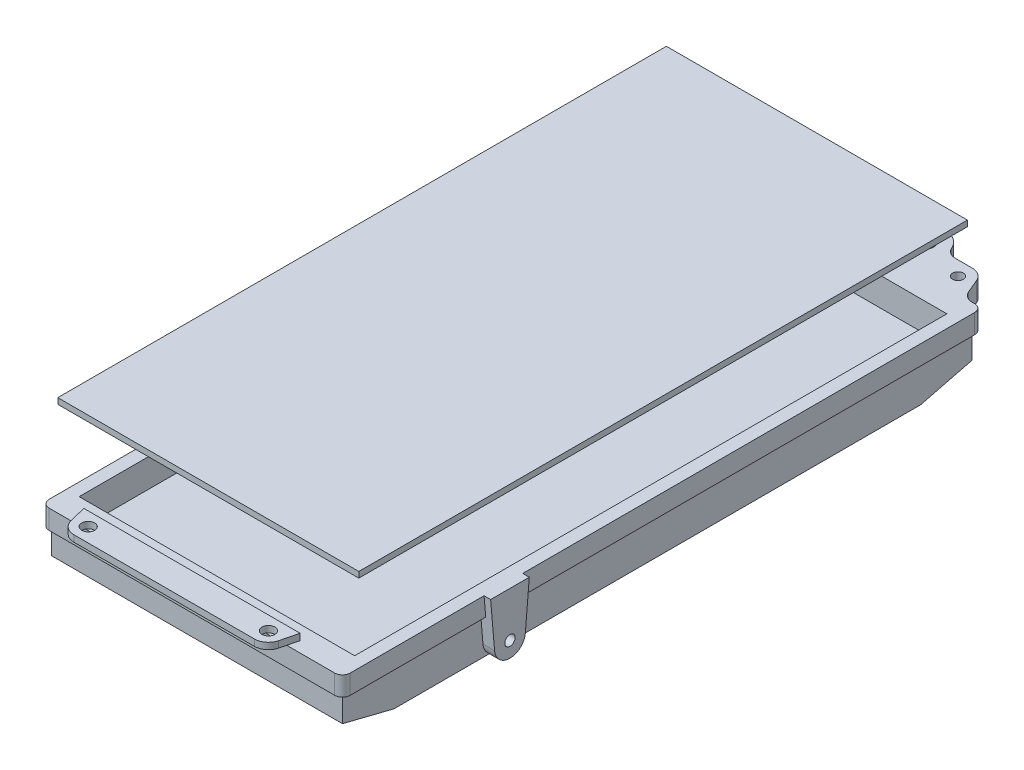
SolidWorks part; units mm, degrees
ref_plane "前视基准面" through (0, 0, 0) normal (0, 0, 1) x (1, 0, 0)
ref_plane "上视基准面" through (0, 0, 0) normal (0, 1, 0) x (1, 0, 0)
ref_plane "右视基准面" through (0, 0, 0) normal (1, 0, 0) x (0, 0, -1)
sketch "草图1" plane through (0, 0, 0) normal (0, 1, 0) x (1, 0, 0)
  line L0 (-25, 135.25) -> (25, 135.25) construction
  line L1 (-58.45, -124.25) -> (58.45, -124.25)
  line L2 (-58.45, -124.25) -> (-58.45, 124.25)
  line L3 (-58.45, 124.25) -> (58.45, 124.25)
  line L4 (58.45, -124.25) -> (58.45, 124.25)
  line L5 (-58.45, -124.25) -> (58.45, 124.25) construction
  line L6 (-58.45, 124.25) -> (58.45, -124.25) construction
  line L7 (-51.5, 124.25) -> (51.5, 124.25)
  line L8 (-51.5, 124.25) -> (-51.5, 136.05)
  line L9 (-51.5, 136.05) -> (51.5, 136.05)
  line L10 (51.5, 124.25) -> (51.5, 136.05)
  line L11 (-43, 130.25) -> (43, 130.25) construction
  circle A0 centre (25, 135.25) radius 3.5
  circle A1 centre (-25, 135.25) radius 3.5
  circle A2 centre (43, 130.25) radius 1.75
  circle A3 centre (-43, 130.25) radius 1.75
  point P0 (0, 0)
  point P14 (0, 135.25)
  point P15 (0, 136.05)
  point P20 (0, 130.25)
  dimension "D4" = 11
  dimension "D5" = 7
  dimension "D6" = 7
  dimension "D9" = 6
  dimension "D11" = 3.5
  dimension "D12" = 3.5
  dimension "D1" = 116.9
  dimension "D2" = 248.5
  dimension "D3" = 11.8
  dimension "D7" = 50
  dimension "D8" = 103
  dimension "D10" = 86
sketch "草图2" plane through (0, 0, 0) normal (0, 1, 0) x (1, 0, 0)
  line L0 (-43, 135.75) -> (-36.4564, 135.75)
  line L1 (-50.3396, 127.0011) -> (-48.0676, 132.3875)
  line L2 (50.3396, 127.0011) -> (48.0676, 132.3875)
  line L3 (-13.5436, 135.75) -> (13.5436, 135.75)
  line L4 (-58.45, 124.25) -> (58.45, 124.25) construction
  line L5 (51.5, 124.25) -> (51.5, 136.05) construction
  line L6 (-51.5, 124.25) -> (-51.5, 136.05) construction
  line L12 (-58.45, -124.25) -> (58.45, -124.25)
  line L13 (58.45, -124.25) -> (58.45, 124.25)
  line L14 (58.45, 124.25) -> (-58.45, 124.25)
  line L15 (-58.45, 124.25) -> (-58.45, -124.25)
  line L16 (-55.45, -124.25) -> (55.45, -124.25)
  line L17 (58.45, -121.25) -> (58.45, 121.25)
  line L18 (55.45, 124.25) -> (54.4858, 124.25)
  line L19 (-58.45, 121.25) -> (-58.45, -121.25)
  line L20 (36.4564, 135.75) -> (43, 135.75)
  line L21 (-54.4858, 124.25) -> (-55.45, 124.25)
  arc A0 (-17.6679, 138.45) -> (-32.3321, 138.45) centre (-25, 135.25) ccw
  circle A1 centre (-25, 135.25) radius 3.5
  circle A2 centre (-25, 135.25) radius 3.5
  circle A3 centre (25, 135.25) radius 3.5
  circle A4 centre (25, 135.25) radius 3.5
  circle A5 centre (-43, 130.25) radius 1.75
  circle A6 centre (-43, 130.25) radius 1.75
  circle A7 centre (43, 130.25) radius 1.75
  circle A8 centre (43, 130.25) radius 1.75
  arc A9 (32.3321, 138.45) -> (17.6679, 138.45) centre (25, 135.25) ccw
  arc A10 (-43, 135.75) -> (-48.0676, 132.3875) centre (-43, 130.25) ccw
  arc A11 (48.0676, 132.3875) -> (43, 135.75) centre (43, 130.25) ccw
  arc A12 (-50.3396, 127.0011) -> (-54.4858, 124.25) centre (-54.4858, 128.75) cw
  arc A13 (-36.4564, 135.75) -> (-32.3321, 138.45) centre (-36.4564, 140.25) ccw
  arc A14 (-13.5436, 135.75) -> (-17.6679, 138.45) centre (-13.5436, 140.25) cw
  arc A15 (13.5436, 135.75) -> (17.6679, 138.45) centre (13.5436, 140.25) ccw
  arc A16 (36.4564, 135.75) -> (32.3321, 138.45) centre (36.4564, 140.25) cw
  arc A17 (50.3396, 127.0011) -> (54.4858, 124.25) centre (54.4858, 128.75) ccw
  arc A18 (-58.45, -121.25) -> (-55.45, -124.25) centre (-55.45, -121.25) ccw
  arc A19 (55.45, -124.25) -> (58.45, -121.25) centre (55.45, -121.25) ccw
  arc A20 (58.45, 121.25) -> (55.45, 124.25) centre (55.45, 121.25) ccw
  arc A21 (-55.45, 124.25) -> (-58.45, 121.25) centre (-55.45, 121.25) ccw
  point P41 (-51.5, 124.25)
  point P52 (51.5, 124.25)
  dimension "D7" = 16
  dimension "D8" = 16
  dimension "D9" = 11
  dimension "D10" = 11
  dimension "D3" = 4.5
  dimension "D11" = 3
  dimension "D1" = 0
  dimension "D2" = 0
  dimension "D4" = 0
  dimension "D5" = 0
  dimension "D6" = 0
extrude "凸台-拉伸1" add sketch "草图2" along normal blind 7.5
sketch "草图3" plane through (0, 0, 0) normal (0, -1, 0) x (1, 0, 0)
  circle A0 centre (25, -135.25) radius 5.25
  circle A1 centre (-25, -135.25) radius 5.25
  dimension "D1" = 10.5
  dimension "D2" = 10.5
extrude "切除-拉伸1" cut sketch "草图3" against normal blind 4
hole_wizard "M5 螺纹孔1" positions "草图4" profile "草图5" tap size "M5" standard "GB" end condition through all
sketch "草图4" plane through (0, 7.5, 0) normal (0, 1, 0) x (1, 0, 0)
  point P0 (-43, 130.25)
  point P2 (43, 130.25)
sketch "草图5" plane through (-43, 7.5, -130.25) normal (1, 0, 0) x (0, 0, 1)
  line L0 (0, 0) -> (0, 7.5)
  line L1 (0, 7.5) -> (2.1, 7.5)
  line L2 (2.1, 7.5) -> (2.1, 0)
  line L5 (2.1, 0) -> (0, 0)
  line L11 (0, -6.35) -> (0, 107.95) construction
  dimension "通孔螺纹孔钻头直径" = 4.2
  dimension "通孔螺纹孔钻头深度" = 7.5
cosmetic thread "孔螺蚊线1" parameters "D1"=31, "D2"=5.2
cosmetic thread "孔螺蚊线2" parameters "D1"=31, "D2"=5.2
sketch "草图6" plane through (0, 0, 0) normal (0, -1, 0) x (1, 0, 0)
  line L1 (56.5, -122.25) -> (-56.5, -122.25)
  line L2 (56.5, -122.25) -> (56.5, 122.3)
  line L3 (56.5, 122.3) -> (-56.5, 122.3)
  line L4 (-56.5, -122.25) -> (-56.5, 122.3)
  line L5 (-55.45, 124.25) -> (55.45, 124.25) construction
  arc A1 (17.6679, -138.45) -> (32.3321, -138.45) centre (25, -135.25) ccw construction
  point P7 (0, -122.25)
  dimension "D1" = 21
  dimension "D2" = 113
  dimension "D3" = 1.95
extrude "凸台-拉伸2" add sketch "草图6" along normal blind 15
sketch "草图7" plane through (-56.5, 0, 0) normal (-1, 0, 0) x (0, 0, 1)
  line L0 (54.25, 7.5) -> (55.7713, -10.5052)
  line L1 (-121.25, 7.5) -> (121.25, 7.5) construction
  line L2 (69.25, 7.5) -> (67.7287, -10.5052)
  line L3 (124.25, 7.5) -> (124.25, 0) construction
  line L4 (54.25, 7.5) -> (69.25, 7.5)
  circle A0 centre (61.75, -10) radius 2
  circle A1 centre (61.75, -10) radius 6
  point P9 (61.75, 7.5)
  line M4 (122.3, 0) -> (-122.25, 0)
  line M6 (-122.25, -15) -> (122.3, -15)
  dimension "D1" = 62.5
  dimension "D2" = 4
  dimension "D3" = 12
  dimension "D4" = 15
  dimension "D5" = 17.5
extrude "凸台-拉伸4" add sketch "草图7" along normal blind 4.5 contours A1 L2 L0 M4 | A1 A0 M6 | L4 L0 L2 M4 | A1 M6 region at (-56.5, 3.8051, 61.75) region at (-56.5, -2.8878, 61.75) region at (-56.5, -4.168, 61.5041) region at (-56.5, -15.403, 61.75)
extrude "凸台-拉伸5" add sketch "草图7<4>" against normal blind 4.5 from surface contours A1 L2 L0 M4 | A1 A0 M6 | L4 L0 L2 M4 | A1 M6 region at (-56.5, 3.8051, 61.75) region at (-56.5, -2.8878, 61.75) region at (-56.5, -4.168, 61.5041) region at (-56.5, -15.403, 61.75) starting at face at (56.5, -7.5, 0.025)
sketch "草图7<4>" plane through (-56.5, 0, 0) normal (-1, 0, 0) x (0, 0, 1) same geometry as "草图7"
sketch "草图8" plane through (-58.45, 0, 0) normal (-1, 0, 0) x (0, 0, 1)
  line L0 (124.25, 7.5) -> (121.25, 7.5) construction
  line L1 (124.25, 14.16) -> (135.05, 14.16)
  line L2 (124.25, 14.16) -> (124.25, 11.66)
  line L3 (124.25, 11.66) -> (135.05, 11.66)
  line L4 (135.05, 14.16) -> (135.05, 11.66)
  line L5 (124.25, 7.5) -> (124.25, 0) construction
  dimension "D1" = 10.8
  dimension "D2" = 2.5
  dimension "D3" = 4.16
extrude "凸台-拉伸6" add sketch "草图8" against normal blind 110 separate body
sketch "草图9" plane through (0, 14.16, 0) normal (0, 1, 0) x (1, 0, 0)
  line L0 (-55.45, -124.25) -> (55.45, -124.25) construction
  line L1 (-42, -124.25) -> (42, -124.25)
  line L5 (-35, -129.55) -> (35, -129.55) construction
  line L6 (-42, -124.25) -> (-40.3347, -130.8883)
  line L7 (42, -124.25) -> (40.3347, -130.8883)
  line L8 (-35, -135.05) -> (35, -135.05)
  line L9 (51.55, -135.05) -> (-58.45, -135.05) construction
  line L14 (-58.45, -124.25) -> (-58.45, -135.05)
  line L15 (-58.45, -135.05) -> (51.55, -135.05)
  line L16 (51.55, -135.05) -> (51.55, -124.25)
  line L17 (51.55, -124.25) -> (-58.45, -124.25)
  line L18 (-58.45, -124.25) -> (-58.45, -135.05)
  line L19 (-58.45, -135.05) -> (51.55, -135.05)
  line L20 (51.55, -135.05) -> (51.55, -124.25)
  line L21 (51.55, -124.25) -> (-58.45, -124.25)
  circle A0 centre (-35, -129.55) radius 5.5
  circle A1 centre (35, -129.55) radius 5.5
  point P10 (0, -129.55)
  point P11 (0, -124.25)
  line M10 (-58.45, -124.25) -> (-58.45, -135.05)
  line M11 (-58.45, -135.05) -> (51.55, -135.05)
  line M12 (51.55, -135.05) -> (51.55, -124.25)
  line M13 (51.55, -124.25) -> (-58.45, -124.25)
  dimension "D2" = 70
  dimension "D3" = 11
  dimension "D4" = 11
  dimension "D1" = 84
  dimension "D5" = 0
extrude "切除-拉伸2" cut sketch "草图9" against normal blind 110 contours A0 L6 M13 M10 M11 | A1 L7 M11 M12 M13 region at (-49.3317, 14.16, 129.8662) region at (45.8502, 14.16, 129.999)
hole_wizard "大小mm 暗销孔1" positions "草图10" profile "草图11" hole size "Ø5.0" standard "GB" end condition through all
sketch "草图10" plane through (0, 14.16, 0) normal (0, 1, 0) x (1, 0, 0)
  point P0 (-35, -129.55)
  point P2 (35, -129.55)
sketch "草图11" plane through (-35, 14.16, 129.55) normal (1, 0, 0) x (0, 0, 1)
  line L0 (0, 0) -> (0, 30.16)
  line L1 (0, 30.16) -> (2.5, 30.16)
  line L2 (2.5, 30.16) -> (2.5, 0)
  line L5 (2.5, 0) -> (0, 0)
  line L11 (0, -6.35) -> (0, 107.95) construction
  dimension "通孔孔直径" = 5
  dimension "通孔孔深度" = 30.16
sketch "草图12" plane through (-56.5, 0, 0) normal (-1, 0, 0) x (0, 0, 1)
  line L0 (-122.25, -10) -> (-102.25, -15)
  line L1 (-122.25, -15) -> (-122.25, 0) construction
  line L2 (58.4334, -15) -> (-122.25, -15) construction
  line L3 (102.3, -15) -> (122.3, -10)
  line L4 (122.3, -15) -> (65.0666, -15) construction
  line L5 (122.3, -15) -> (122.3, 0) construction
  line L10 (55.7713, -10.5052) -> (54.8837, 0)
  line L11 (54.8837, 0) -> (-122.25, 0)
  line L12 (-122.25, 0) -> (-122.25, -15)
  line L13 (-122.25, -15) -> (58.4334, -15)
  line L14 (55.7713, -10.5052) -> (54.8837, 0)
  line L15 (54.8837, 0) -> (-122.25, 0)
  line L16 (-122.25, 0) -> (-122.25, -15)
  line L17 (-122.25, -15) -> (58.4334, -15)
  line L18 (65.0666, -15) -> (122.3, -15)
  line L19 (122.3, -15) -> (122.3, 0)
  line L20 (122.3, 0) -> (68.6163, 0)
  line L21 (68.6163, 0) -> (67.7287, -10.5052)
  line L22 (65.0666, -15) -> (122.3, -15)
  line L23 (122.3, -15) -> (122.3, 0)
  line L24 (122.3, 0) -> (68.6163, 0)
  line L25 (68.6163, 0) -> (67.7287, -10.5052)
  arc A1 (55.7713, -10.5052) -> (58.4334, -15) centre (61.75, -10) ccw
  arc A2 (55.7713, -10.5052) -> (58.4334, -15) centre (61.75, -10) ccw
  arc A3 (65.0666, -15) -> (67.7287, -10.5052) centre (61.75, -10) ccw
  arc A4 (65.0666, -15) -> (67.7287, -10.5052) centre (61.75, -10) ccw
  line M8 (-122.25, 0) -> (-122.25, -15)
  line M9 (-122.25, -15) -> (58.4334, -15)
  dimension "D1" = 5
  dimension "D2" = 20
  dimension "D3" = 20
  dimension "D4" = 5
  dimension "D5" = 0
  dimension "D6" = 0
extrude "切除-拉伸3" cut sketch "草图12" against normal through all contours L22 L23 L3 | L0 M8 M9 region at (-56.5, -13.3333, -115.5833) region at (-56.5, -13.3333, 115.6333)
sketch "草图13" plane through (58.45, 0, 0) normal (1, 0, 0) x (0, 0, -1)
  line L0 (-121.25, 7.5) -> (-69.25, 7.5) construction
  line L1 (-117.8985, 40) -> (118.4553, 40)
  line L2 (-117.8985, 40) -> (-117.8985, 37.7374)
  line L3 (-117.8985, 37.7374) -> (118.4553, 37.7374)
  line L4 (118.4553, 40) -> (118.4553, 37.7374)
  dimension "D1" = 32.5
extrude "凸台-拉伸7" add sketch "草图13" against normal up to surface (116.9 mm away) separate body up to face at (-58.45, 3.75, -33.3416)
sketch "草图14" plane through (0, 7.5, 0) normal (0, 1, 0) x (1, 0, 0)
  line L0 (56.5, 122.25) -> (56.5, 102.25) construction
  line L1 (-56.5, 102.25) -> (-56.5, 122.25) construction
  line L2 (-56.5, 122.25) -> (56.5, 122.25) construction
  line L3 (56.5, -102.3) -> (56.5, -122.3) construction
  line L4 (56.5, -122.3) -> (-56.5, -122.3) construction
  line L5 (-56.5, -122.3) -> (-56.5, -102.3) construction
  line L6 (56.5, -65.0666) -> (56.5, -102.3) construction
  line L7 (-56.5, -102.3) -> (-56.5, -65.0666) construction
  line L8 (-56.5, -65.0666) -> (-56.5, -58.4334) construction
  line L9 (-56.5, -58.4334) -> (-56.5, 102.25) construction
  line L10 (56.5, 102.25) -> (56.5, -58.4334) construction
  line L11 (56.5, -58.4334) -> (56.5, -65.0666) construction
  line L12 (56.5, 122.25) -> (56.5, 102.25)
  line L13 (-56.5, 102.25) -> (-56.5, 122.25)
  line L14 (-56.5, 122.25) -> (56.5, 122.25)
  line L15 (56.5, -102.3) -> (56.5, -122.3)
  line L16 (56.5, -122.3) -> (-56.5, -122.3)
  line L17 (-56.5, -122.3) -> (-56.5, -102.3)
  line L18 (56.5, -65.0666) -> (56.5, -102.3)
  line L19 (-56.5, -102.3) -> (-56.5, -65.0666)
  line L20 (-56.5, -65.0666) -> (-56.5, -58.4334)
  line L21 (-56.5, -58.4334) -> (-56.5, 102.25)
  line L22 (56.5, 102.25) -> (56.5, -58.4334)
  line L23 (56.5, -58.4334) -> (56.5, -65.0666)
  line L24 (53.5, -119.3) -> (-53.5, -119.3)
  line L25 (-53.5, -119.3) -> (-53.5, -102.3)
  line L26 (-53.5, -102.3) -> (-53.5, -65.0666)
  line L27 (-53.5, -65.0666) -> (-53.5, -58.4334)
  line L28 (-53.5, -58.4334) -> (-53.5, 102.25)
  line L29 (-53.5, 102.25) -> (-53.5, 119.25)
  line L30 (-53.5, 119.25) -> (53.5, 119.25)
  line L31 (53.5, 119.25) -> (53.5, 102.25)
  line L32 (53.5, 102.25) -> (53.5, -58.4334)
  line L33 (53.5, -58.4334) -> (53.5, -65.0666)
  line L34 (53.5, -65.0666) -> (53.5, -102.3)
  line L35 (53.5, -102.3) -> (53.5, -119.3)
  line L36 (53.5, -114.5597) -> (-53.5, -114.5597)
  line L37 (53.5, 115.4403) -> (-53.5, 115.4403)
  dimension "D2" = 230
  dimension "D1" = 3
extrude "切除-拉伸4" cut sketch "草图14" against normal blind 11 contours L35 L34 L33 L32 L31 L30 L29 L28 L27 L26 L25 L24 region at (0, 7.5, -0.4403)
